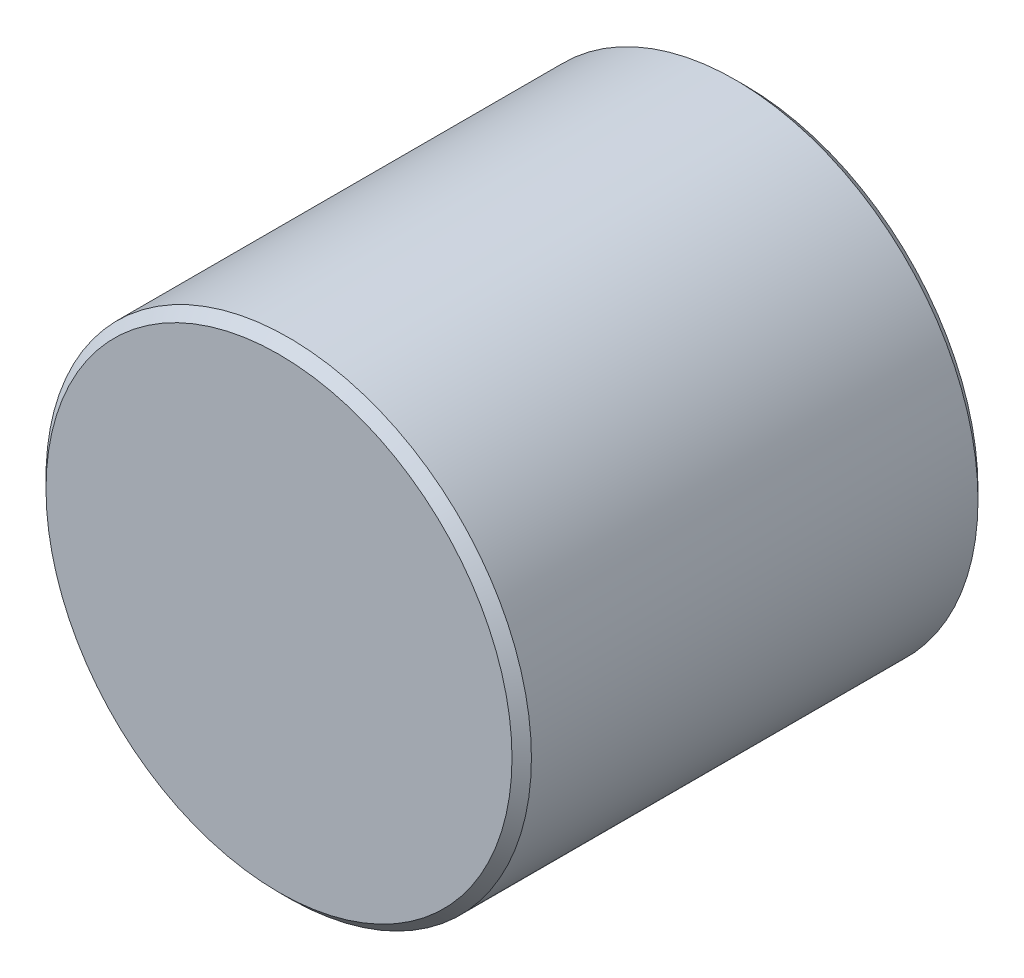
SolidWorks part; units mm, degrees
ref_plane "Front Plane" through (0, 0, 0) normal (0, 0, 1) x (1, 0, 0)
ref_plane "Top Plane" through (0, 0, 0) normal (0, 1, 0) x (1, 0, 0)
ref_plane "Right Plane" through (0, 0, 0) normal (1, 0, 0) x (0, 0, -1)
sketch "Sketch1" plane through (0, 0, 0) normal (0, 0, 1) x (1, 0, 0)
  circle A0 centre (0, 0) radius 2.5
  dimension "D1" = 5
extrude "Boss-Extrude1" add sketch "Sketch1" along normal blind 4.8
chamfer "Chamfer1" distance 0.1 angle 45 2 edges at (2.5, 0, 0) (2.5, 0, 4.8)
